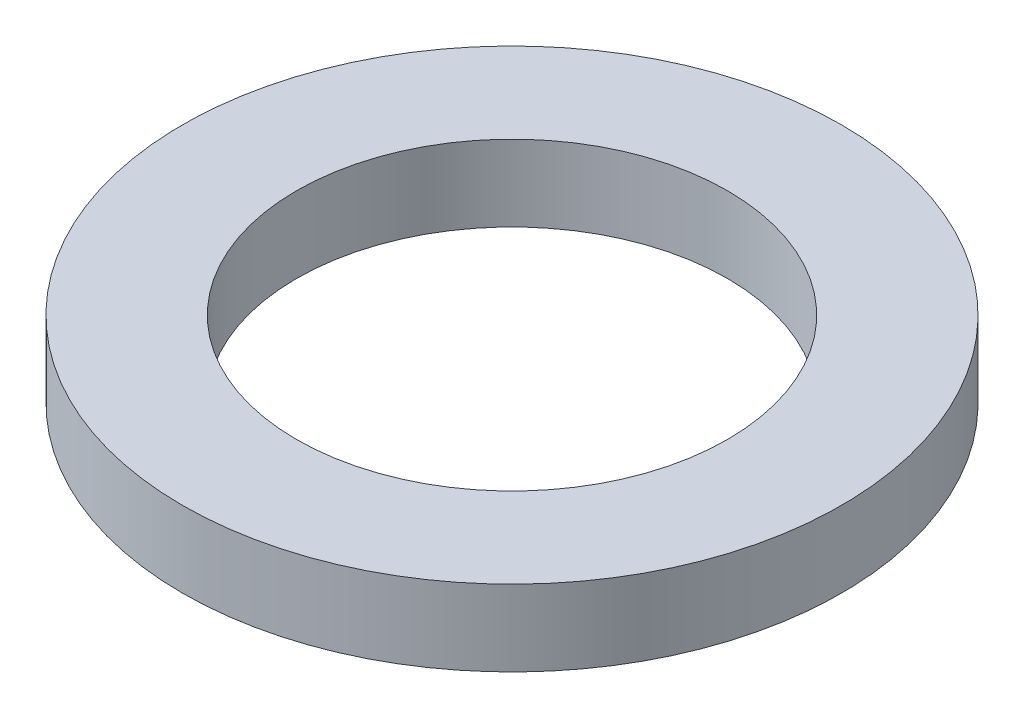
SolidWorks part; units mm, degrees
ref_plane "Front Plane" through (0, 0, 0) normal (0, 0, 1) x (1, 0, 0)
ref_plane "Top Plane" through (0, 0, 0) normal (0, 1, 0) x (1, 0, 0)
ref_plane "Right Plane" through (0, 0, 0) normal (1, 0, 0) x (0, 0, -1)
sketch "Sketch1" plane through (0, 0, 0) normal (0, 1, 0) x (1, 0, 0)
  circle A0 centre (0, 0) radius 65
  dimension "FLANGE_OD" = 130
extrude "Boss-Extrude1" add sketch "Sketch1" along normal blind 15
sketch "Sketch2" plane through (0, 0, 0) normal (0, 1, 0) x (1, 0, 0)
  circle A0 centre (0, 0) radius 42.5
  dimension "BORE_D" = 85
extrude "Cut-Extrude1" cut sketch "Sketch2" along normal through all
sketch "Sketch3" plane through (0, 15, 0) normal (0, 1, 0) x (1, 0, 0)
  circle A0 centre (0, 0) radius 30.278 construction
  circle A1 centre (-30.278, 0) radius 2.4652
  dimension "BOLT_D" = 4.9304
  dimension "BOLT_PCD" = 60.556
extrude "Cut-Extrude2" cut sketch "Sketch3" against normal blind 14.172 rebuild error yes
pattern_circular "CirPattern1" count 8 over 360 rebuild error yes
